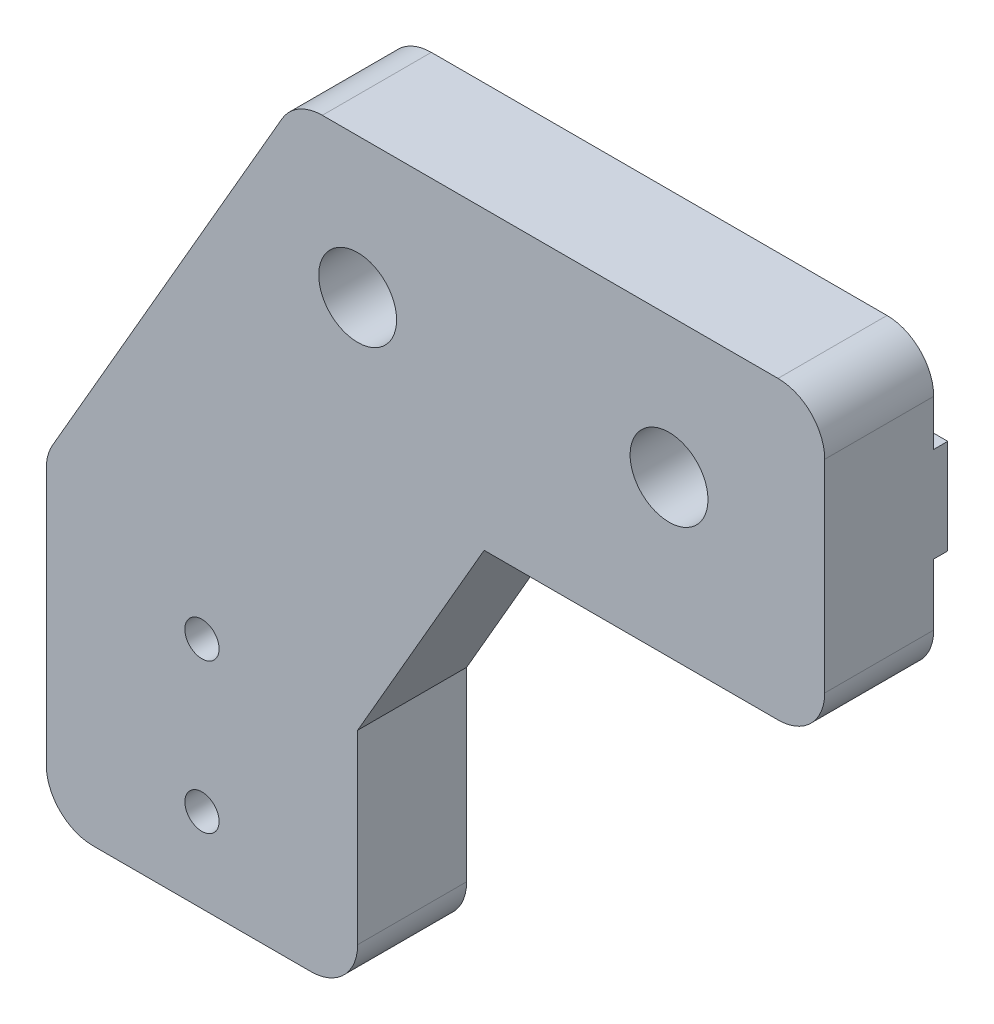
SolidWorks part; units mm, degrees
material "ABS"
ref_plane "Front Plane" through (0, 0, 0) normal (0, 0, 1) x (1, 0, 0)
ref_plane "Top Plane" through (0, 0, 0) normal (0, 1, 0) x (1, 0, 0)
ref_plane "Right Plane" through (0, 0, 0) normal (1, 0, 0) x (0, 0, -1)
sketch "Sketch1" plane through (0, 0, 0) normal (0, 0, 1) x (1, 0, 0)
  line L0 (3, 0) -> (17, 0)
  line L1 (20, 3) -> (20, 14.9282)
  line L2 (28.1244, 29) -> (47, 29)
  line L3 (50, 32) -> (50, 45)
  line L4 (47, 48) -> (17.7321, 48)
  line L5 (0, 19.4833) -> (0, 3)
  line L6 (10, 39) -> (50, 39) construction
  line L7 (20, 14.9282) -> (28.1244, 29)
  line L8 (10, 0) -> (10, 48) construction
  line L9 (15.134, 46.5) -> (0.4019, 20.9833)
  circle A0 centre (20, 39) radius 2.5
  circle A1 centre (40, 39) radius 2.5
  circle A2 centre (10, 5.4) radius 1.1
  circle A3 centre (10, 15) radius 1.1
  arc A5 (47, 29) -> (50, 32) centre (47, 32) ccw
  arc A6 (50, 45) -> (47, 48) centre (47, 45) ccw
  arc A7 (0, 19.4833) -> (0.4019, 20.9833) centre (3, 19.4833) cw
  arc A8 (0, 3) -> (3, 0) centre (3, 3) ccw
  arc A9 (17, 0) -> (20, 3) centre (17, 3) ccw
  arc A10 (15.134, 46.5) -> (17.7321, 48) centre (17.7321, 45) cw
  point P26 (50, 29)
  point P29 (50, 48)
  point P32 (0, 48)
  point P35 (0, 0)
  point P38 (20, 0)
  point P41 (16, 48)
  dimension "D5" = 5
  dimension "D6" = 5
  dimension "D7" = 20
  dimension "D8" = 10
  dimension "D10" = 2.2
  dimension "D11" = 2.2
  dimension "D12" = 5.4
  dimension "D13" = 9.6
  dimension "D14" = 20
  dimension "D15" = 3
  dimension "D18" = 3
  dimension "D19" = 3
  dimension "D1" = 48
  dimension "D2" = 20
  dimension "D3" = 50
  dimension "D4" = 19
  dimension "D9" = 9
  dimension "D16" = 120
  dimension "D17" = 16
extrude "Boss-Extrude1" add sketch "Sketch1" along normal blind 7
ref_axis "Axis1" through (40, 39, 7) along (0, 0, -1)
sketch "Sketch2" plane through (50, 0, 0) normal (1, 0, 0) x (0, 0, -1)
  line L0 (0, 32) -> (0, 45) construction
  line L1 (0, 42.05) -> (0.9, 42.05)
  line L2 (0, 42.05) -> (0, 35.95)
  line L3 (0, 35.95) -> (0.9, 35.95)
  line L4 (0.9, 42.05) -> (0.9, 35.95)
  line L5 (-7, 39) -> (0, 39) construction
  point P6 (0, 39)
  dimension "D1" = 6.1
  dimension "D2" = 0.9
extrude "Boss-Extrude2" add sketch "Sketch2" against normal up to surface (37.4352 mm away) contours L3 L4 L1 L2 up to face at (7.7679, 33.7417, 3.5)
sketch "Sketch3" plane through (0, 0, 0) normal (0, 0, 1) x (1, 0, 0)
  circle A0 centre (20, 39) radius 2.5 construction
  circle A1 centre (40, 39) radius 2.5 construction
  circle A2 centre (20, 39) radius 2.5
  circle A3 centre (40, 39) radius 2.5
extrude "Cut-Extrude1" cut sketch "Sketch3" against normal up to next
